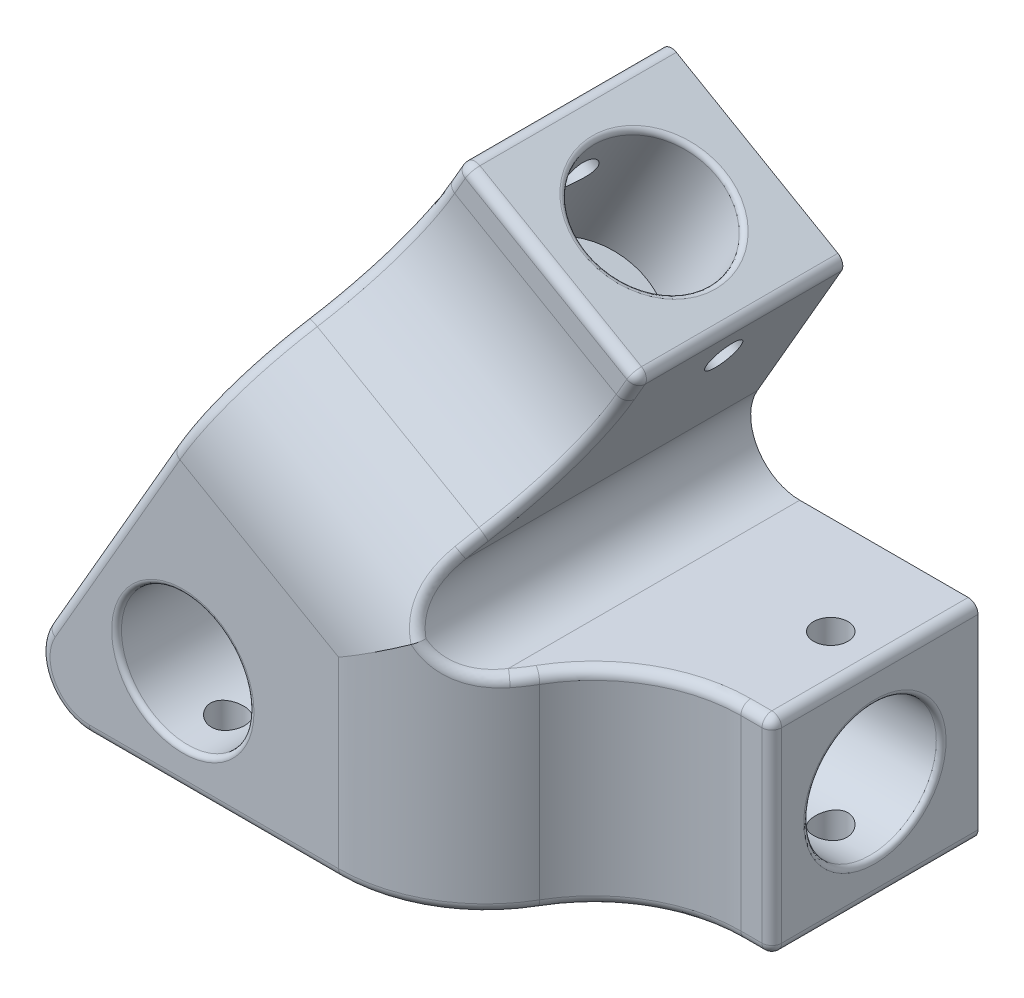
SolidWorks part; units mm, degrees
other "Corner Joint"
ref_plane "Front Plane" through (0, 0, 0) normal (0, 0, 1) x (1, 0, 0)
ref_plane "Top Plane" through (0, 0, 0) normal (0, 1, 0) x (1, 0, 0)
ref_plane "Right Plane" through (0, 0, 0) normal (1, 0, 0) x (0, 0, -1)
sketch "Sketch1" plane through (0, 0, 0) normal (0, 0, 1) x (1, 0, 0)
  line L0 (0, 0) -> (45, 0) construction
  line L1 (0, 0) -> (22.5, 38.9711) construction
  line L16 (45, -10.5) -> (-9.5263, -10.5)
  line L17 (16.8708, 42.2211) -> (28.1292, 35.7211) construction
  line L18 (16.8708, 42.2211) -> (9.3708, 29.2308) construction
  line L19 (9.3708, 29.2308) -> (20.6292, 22.7308) construction
  line L20 (28.1292, 35.7211) -> (20.6292, 22.7308) construction
  line L21 (30, 6.5) -> (45, 6.5) construction
  line L22 (30, 6.5) -> (30, -6.5) construction
  line L23 (30, -6.5) -> (45, -6.5) construction
  line L24 (45, 6.5) -> (45, -6.5) construction
  line L25 (-13.8564, -3) -> (13.4067, 44.2211)
  line L26 (13.4067, 44.2211) -> (31.5933, 33.7211)
  line L27 (31.5933, 33.7211) -> (22.5167, 18)
  line L28 (26.8468, 10.5) -> (45, 10.5)
  line L29 (45, 10.5) -> (45, -10.5)
  circle A0 centre (0, 0) radius 6.5 construction
  arc A1 (26.8468, 10.5) -> (22.5167, 18) centre (26.8468, 15.5) cw
  arc A2 (-9.5263, -10.5) -> (-13.8564, -3) centre (-9.5263, -5.5) cw
  point P2 (22.5, 38.9711)
  point P12 (45, 0)
  dimension "D7" = 15
  dimension "D8" = 13
  dimension "D13" = 5
  dimension "D1" = 60
  dimension "D2" = 45
  dimension "D3" = 45
  dimension "D4" = 13
  dimension "D5" = 15
  dimension "D6" = 13
  dimension "D9" = 4
  dimension "D10" = 4
  dimension "D11" = 4
  dimension "D12" = 4
extrude "Boss-Extrude3" add sketch "Sketch1" along normal blind 21
sketch "Sketch3" plane through (0, 0, 21) normal (0, 0, 1) x (1, 0, 0)
  line L0 (22.5167, 18) -> (4.3301, 28.5)
  line L1 (-13.8564, -3) -> (13.4067, 44.2211) construction
  line L2 (26.8468, 10.5) -> (26.8468, -10.5)
  line L3 (45, -10.5) -> (-9.5263, -10.5) construction
  line L4 (13.4067, 44.2211) -> (31.5933, 33.7211) construction
  line L5 (4.3301, 28.5) -> (-13.8564, -3)
  line L6 (-9.5263, -10.5) -> (26.8468, -10.5)
  line L7 (26.8468, 10.5) -> (26.6736, 10.5)
  line L8 (22.4301, 17.85) -> (22.5167, 18)
  line L9 (31.5933, 33.7211) -> (22.5167, 18) construction
  line L10 (26.8468, 10.5) -> (45, 10.5) construction
  circle A0 centre (0, 0) radius 6.75
  arc A1 (-9.5263, -10.5) -> (-13.8564, -3) centre (-9.5263, -5.5) cw
  arc A3 (22.5167, 18) -> (26.8468, 10.5) centre (26.8468, 15.5) ccw
  arc M12 (26.8468, 10.5) -> (22.5167, 18) centre (26.8468, 15.5) cw
  line M15 (13.4067, 44.2211) -> (-13.8564, -3)
  arc M16 (-13.8564, -3) -> (-9.5263, -10.5) centre (-9.5263, -5.5) ccw
  line M17 (-9.5263, -10.5) -> (45, -10.5)
  dimension "D1" = 5
  dimension "D2" = 13.5
extrude "Boss-Extrude4" add sketch "Sketch3" along normal blind 15 contours L2 L0 A0 M12 M15 M16 M17 region at (9.2242, 5.3256, 21)
sketch "Sketch4" plane through (45, 0, 0) normal (1, 0, 0) x (0, 0, -1)
  line L0 (-21, -10.5) -> (-21, 10.5) construction
  line L1 (-21, -10.5) -> (0, -10.5) construction
  circle A0 centre (-10.5, 0) radius 6.75
  dimension "D1" = 13.5
  dimension "D2" = 10.5
  dimension "D3" = 10.5
extrude "Cut-Extrude1" cut sketch "Sketch4" against normal blind 15
sketch "Sketch5" plane through (22.5, 38.9711, 0) normal (0.5, 0.866, 0) x (0.866, -0.5, 0)
  line L0 (-10.5, -21) -> (-10.5, 0) construction
  line L1 (10.5, 0) -> (-10.5, 0) construction
  circle A0 centre (0, -10.5) radius 6.75
  dimension "D1" = 13.5
  dimension "D2" = 10.5
  dimension "D3" = 10.5
extrude "Cut-Extrude2" cut sketch "Sketch5" against normal blind 15
fillet "Fillet1" radius 15 2 edges at (13.4234, 23.25, 21) (26.8468, 0, 21)
fillet "Fillet2" radius 15 2 edges at (26.8468, 0, 36) (13.4234, 23.25, 36)
fillet "Fillet3" radius 1 23 edges at (24.1108, 11.315, 33.5309) (27.9284, 10.5, 29.9162) (43.4234, 10.5, 21) (30.805, 32.3558, 21) (21.8979, 16.2133, 32.906) (23.0575, 18.9367, 29.9162) (43.4234, -10.5, 21) (34.3468, -10.5, 23.0096) (23.366, -10.5, 33.9904) (3.1699, -10.5, 36) (-13.8564, -8, 36) (-7.5083, 7.9952, 36) (2.5897, 25.4856, 33.9904) (12.6184, 42.8558, 21) (45, -10.5, 10.5) (45, 10.5, 10.5) (45, 0, 21) (34.3468, 10.5, 23.0096) (31.5933, 33.7211, 10.5) (22.5, 38.9711, 21) (26.2667, 24.4952, 23.0096) (8.0801, 34.9952, 23.0096) (13.4067, 44.2211, 10.5)
fillet "Fillet4" radius 0.5 3 edges at (45, 6.75, 10.5) (16.6543, 42.3461, 10.5) (6.75, 0, 36)
sketch "Sketch6" plane through (0, -10.5, 0) normal (0, -1, 0) x (1, 0, 0)
  line L0 (-9.5263, 2) -> (44, 2) construction
  line L1 (-9.5263, 35) -> (-9.5263, 0) construction
  line L2 (44, 0) -> (44, 20) construction
  line L3 (-9.5263, 0) -> (44, 0) construction
  text T0 " V1.1" font "Georgia" height in points 18
  dimension "D1" = 2
extrude "Cut-Extrude3" cut sketch "Sketch6" against normal blind 0.5
sketch "Sketch7" plane through (0, -10.5, 0) normal (0, -1, 0) x (1, 0, 0)
  line L0 (45, 20) -> (45, 0) construction
  line L1 (-9.5263, 36) -> (15.866, 36) construction
  circle A0 centre (40, 10) radius 1.75
  circle A1 centre (-0.4147, 31) radius 1.75
  point P4 (45, 10)
  dimension "D1" = 3.5
  dimension "D2" = 5
  dimension "D3" = 5
extrude "Cut-Extrude4" cut sketch "Sketch7" against normal blind 22
sketch "Sketch8" plane through (-9.0933, 5.25, 0) normal (-0.866, 0.5, 0) x (0, 0, 1)
  line L0 (0, 45) -> (20, 45) construction
  circle A0 centre (10, 40) radius 1.75
  point P5 (10, 45)
  dimension "D1" = 3.5
  dimension "D2" = 5
extrude "Cut-Extrude5" cut sketch "Sketch8" against normal blind 24
